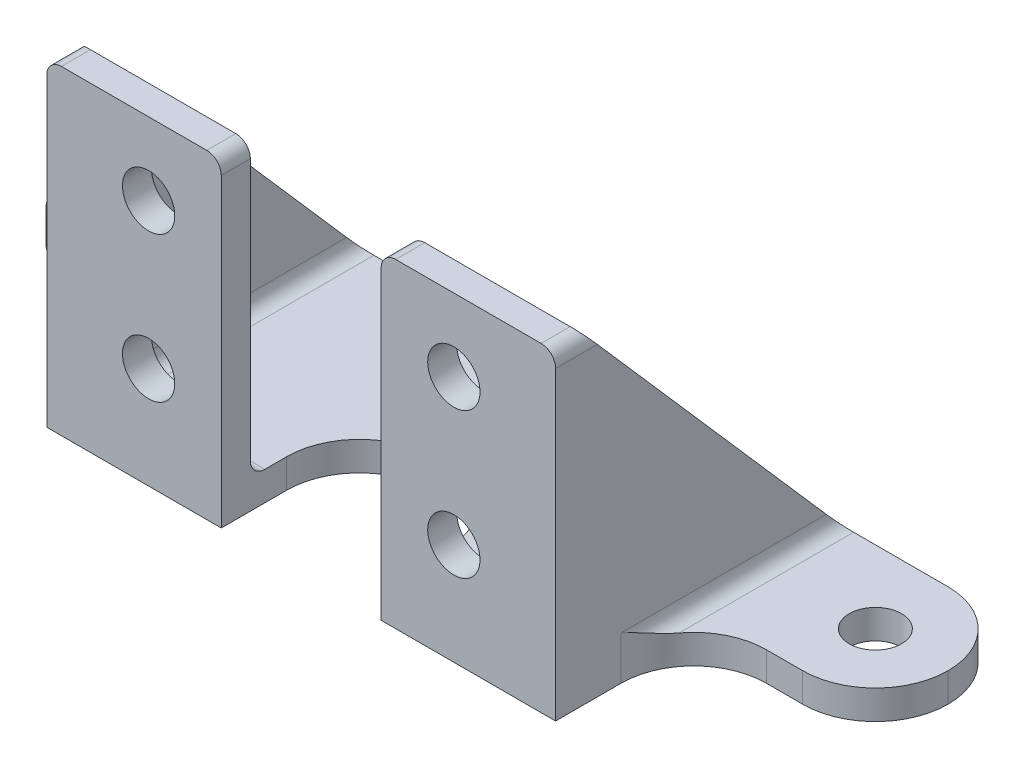
SolidWorks part; units mm, degrees
ref_plane "Front Plane" through (0, 0, 0) normal (0, 0, 1) x (1, 0, 0)
ref_plane "Top Plane" through (0, 0, 0) normal (0, 1, 0) x (1, 0, 0)
ref_plane "Right Plane" through (0, 0, 0) normal (1, 0, 0) x (0, 0, -1)
sketch "Sketch1" plane through (0, 0, 0) normal (0, 1, 0) x (1, 0, 0)
  line L0 (-12.5, 19.5) -> (47.5, 19.5)
  line L1 (47.5, 19.5) -> (47.5, 9.5)
  line L2 (47.5, 9.5) -> (35, 9.5)
  line L3 (35, 9.5) -> (35, 0)
  line L4 (35, 0) -> (23, 0)
  line L5 (23, 0) -> (23, 9.5)
  line L6 (23, 9.5) -> (12, 9.5)
  line L7 (12, 9.5) -> (12, 0)
  line L8 (12, 0) -> (0, 0)
  line L9 (0, 0) -> (0, 9.5)
  line L10 (0, 9.5) -> (-12.5, 9.5)
  line L11 (-12.5, 9.5) -> (-12.5, 19.5)
  circle A0 centre (-7.5, 14.5) radius 1.8
  circle A1 centre (42.5, 14.5) radius 1.8
  point P17 (-12.5, 14.5)
  dimension "D6" = 3.6
  dimension "D1" = 10
  dimension "D2" = 9.5
  dimension "D3" = 60
  dimension "D4" = 12
  dimension "D5" = 12.5
  dimension "D7" = 50
  dimension "D8" = 5
extrude "Boss-Extrude1" add sketch "Sketch1" along normal blind 2
sketch "Sketch2" plane through (0, 2, 0) normal (0, 1, 0) x (1, 0, 0)
  line L5 (35, 0) -> (35, 9.5) construction
  line L6 (23, 0) -> (35, 0)
  line L7 (23, 0) -> (23, 2)
  line L8 (23, 2) -> (35, 2)
  line L9 (35, 0) -> (35, 2)
  line L10 (12, 0) -> (12, 9.5) construction
  line L11 (0, 0) -> (12, 0)
  line L12 (0, 0) -> (0, 2)
  line L13 (0, 2) -> (12, 2)
  line L14 (12, 0) -> (12, 2)
  dimension "D1" = 2
extrude "Boss-Extrude2" add sketch "Sketch2" along normal blind 20
sketch "Sketch3" plane through (0, 0, -2) normal (0, 0, -1) x (-1, 0, 0)
  line L0 (-35, 22) -> (-23, 22) construction
  line L3 (-12, 22) -> (-12, 2) construction
  line L4 (-23, 22) -> (-23, 2) construction
  circle A0 centre (-7, 7) radius 1.8
  circle A1 centre (-7, 17) radius 1.8
  circle A2 centre (-28, 7) radius 1.8
  circle A3 centre (-28, 17) radius 1.8
  dimension "D1" = 3.6
  dimension "D2" = 10
  dimension "D3" = 5
  dimension "D4" = 5
  dimension "D5" = 5
extrude "Cut-Extrude1" cut sketch "Sketch3" against normal through all
sketch "Sketch4" plane through (0, 0, 0) normal (-1, 0, 0) x (0, 0, 1)
  line L0 (-2, 22) -> (-2, 2)
  line L1 (-2, 2) -> (-19.5, 2)
  line L2 (-19.5, 2) -> (-2, 22)
  dimension "D1" = 17.5
extrude "Boss-Extrude3" add sketch "Sketch4" against normal blind 2
sketch "Sketch5" plane through (35, 0, 0) normal (1, 0, 0) x (0, 0, -1)
  line L0 (2, 22) -> (2, 2)
  line L1 (2, 2) -> (19.5, 2)
  line L2 (19.5, 2) -> (2, 22)
  dimension "D1" = 17.5
extrude "Boss-Extrude4" add sketch "Sketch5" against normal blind 2
fillet "Fillet1" radius 5 4 edges at (35, 1, -9.5) (23, 1, -9.5) (12, 1, -9.5) (0, 1, -9.5)
fillet "Fillet2" radius 5 4 edges at (47.5, 1, -9.5) (47.5, 1, -19.5) (-12.5, 1, -19.5) (-12.5, 1, -9.5)
fillet "Fillet3" radius 1 8 edges at (35, 2, -12) (0, 2, -12) (33, 12, -2) (33, 2, -10.75) (28, 2, -2) (7, 2, -2) (2, 12, -2) (2, 2, -10.75)
fillet "Fillet4" radius 1 4 edges at (35, 22, -1) (23, 22, -1) (12, 22, -1) (0, 22, -1)
